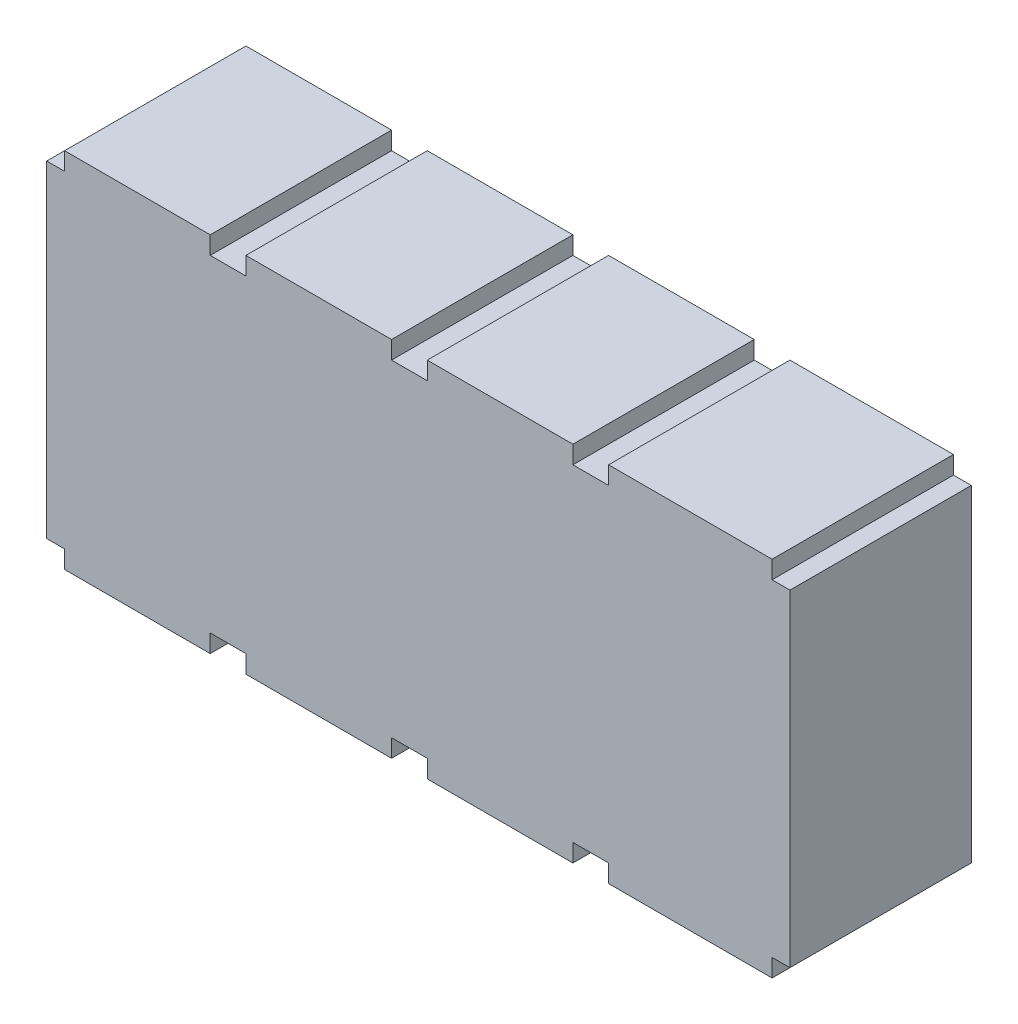
SolidWorks part; units mm, degrees
ref_plane "前视基准面" through (0, 0, 0) normal (0, 0, 1) x (1, 0, 0)
ref_plane "上视基准面" through (0, 0, 0) normal (0, 1, 0) x (1, 0, 0)
ref_plane "右视基准面" through (0, 0, 0) normal (1, 0, 0) x (0, 0, -1)
sketch "草图1" plane through (0, 0, 0) normal (0, 0, 1) x (1, 0, 0)
  line L0 (5.08, 2.29) -> (5.08, 2.54)
  line L1 (5.33, 0) -> (5.33, 2.29)
  line L2 (5.08, 2.54) -> (2.79, 2.54)
  line L3 (-5.08, 2.29) -> (-5.08, -2.29)
  line L4 (-4.83, -2.54) -> (-2.79, -2.54)
  line L5 (5.33, -2.29) -> (5.33, 0)
  line L7 (0.25, 2.54) -> (0.25, 2.29)
  line L8 (0.25, 2.29) -> (-0.25, 2.29)
  line L9 (-0.25, 2.29) -> (-0.25, 2.54)
  line L10 (-2.29, 2.54) -> (-2.29, 2.29)
  line L11 (-2.29, 2.29) -> (-2.79, 2.29)
  line L12 (-2.79, 2.29) -> (-2.79, 2.54)
  line L13 (-4.83, 2.54) -> (-4.83, 2.29)
  line L14 (-4.83, 2.29) -> (-5.08, 2.29)
  line L17 (2.79, 2.54) -> (2.79, 2.29)
  line L18 (2.79, 2.29) -> (2.29, 2.29)
  line L19 (2.29, 2.29) -> (2.29, 2.54)
  line L20 (2.29, 2.54) -> (0.25, 2.54)
  line L21 (5.33, 2.29) -> (5.08, 2.29)
  line L23 (0.25, 2.54) -> (2.29, 2.54) construction
  line L24 (2.79, -2.54) -> (5.08, -2.54)
  line L25 (0.25, -2.54) -> (2.29, -2.54)
  line L26 (5.33, -2.29) -> (5.08, -2.29)
  line L27 (5.08, -2.29) -> (5.08, -2.54)
  line L28 (2.79, -2.54) -> (2.79, -2.29)
  line L29 (2.79, -2.29) -> (2.29, -2.29)
  line L30 (2.29, -2.29) -> (2.29, -2.54)
  line L31 (0.25, -2.54) -> (0.25, -2.29)
  line L32 (0.25, -2.29) -> (-0.25, -2.29)
  line L33 (-0.25, -2.29) -> (-0.25, -2.54)
  line L34 (-2.29, -2.54) -> (-2.29, -2.29)
  line L35 (-2.29, -2.29) -> (-2.79, -2.29)
  line L36 (-2.79, -2.29) -> (-2.79, -2.54)
  line L37 (-4.83, -2.54) -> (-4.83, -2.29)
  line L39 (-4.83, -2.29) -> (-5.08, -2.29)
  line L40 (-2.29, -2.54) -> (-0.25, -2.54)
  line L41 (5.33, 2.54) -> (5.33, 2.29) [skipped]
  line L42 (-2.79, 2.54) -> (-4.83, 2.54)
  line L43 (-0.25, 2.54) -> (-2.29, 2.54)
  line L44 (-0.25, 2.54) -> (-2.29, 2.54) construction
  line L45 (-5.33, 2.29) -> (-5.33, 2.54) [skipped]
  line L46 (4.83, 2.29) -> (4.83, 2.54) [skipped]
  dimension "D1" = 3
  dimension "D3" = 3
extrude "凸台-拉伸1" add sketch "草图1" along normal blind 2.54
